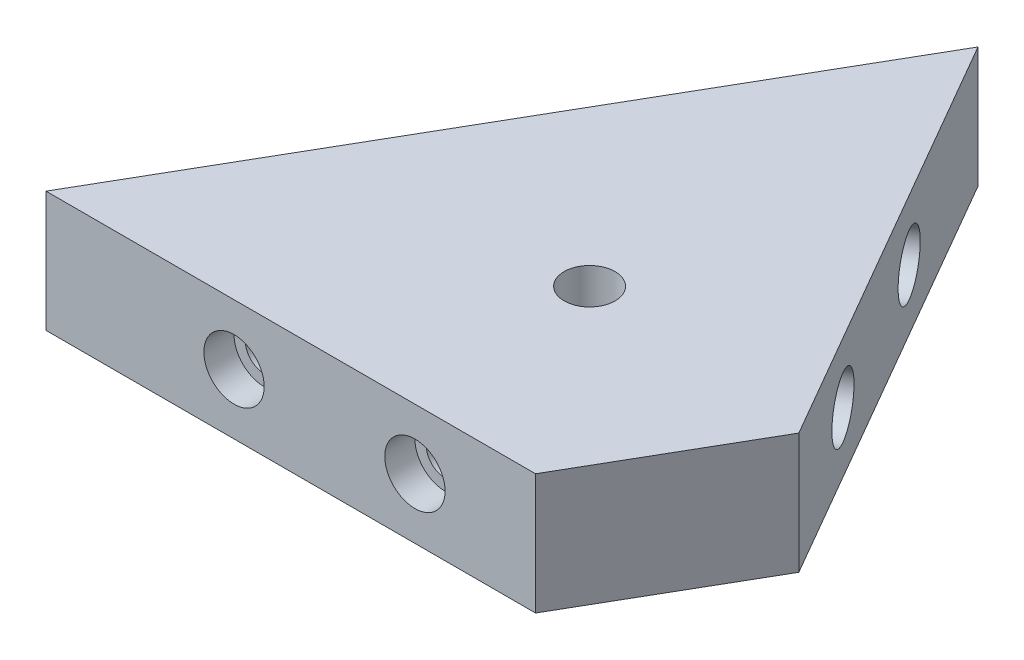
SolidWorks part; units mm, degrees
material "Cast Carbon Steel"
ref_plane "Front Plane" through (0, 0, 0) normal (0, 0, 1) x (1, 0, 0)
ref_plane "Top Plane" through (0, 0, 0) normal (0, 1, 0) x (1, 0, 0)
ref_plane "Right Plane" through (0, 0, 0) normal (1, 0, 0) x (0, 0, -1)
sketch "Sketch1" plane through (0, 0, 0) normal (0, 1, 0) x (1, 0, 0)
  line L0 (159.6594, -241.1624) -> (-297.5406, 22.8022) construction
  line L1 (-145.1406, 286.7667) -> (-449.9406, -241.1624) construction
  line L2 (-449.9406, -241.1624) -> (159.6594, -241.1624) construction
  line L3 (159.6594, -241.1624) -> (-145.1406, 286.7667) construction
  line L4 (93.6683, -241.1624) -> (93.6683, -203.0624) construction
  line L5 (119.0683, -241.1624) -> (129.2161, -223.5859)
  line L6 (55.5683, -241.1624) -> (55.5683, -181.0653) construction
  line L7 (15.9736, -241.1624) -> (51.8951, -178.9446)
  line L8 (15.9736, -241.1624) -> (119.0683, -241.1624)
  line L9 (51.8951, -178.9446) -> (129.2161, -223.5859)
  line L10 (93.6683, -203.0624) -> (55.5683, -203.0624) construction
  dimension "D1" = 609.6
  dimension "D2" = 38.1
  dimension "D3" = 25.4
  dimension "D4" = 38.1
  dimension "D5" = 15.24
  dimension "D6" = 40.5911
  dimension "D7" = 103.0947
  dimension "D8" = 60
  dimension "D9" = 120
extrude "Boss-Extrude1" add sketch "Sketch1" along normal blind 25.4
sketch "Sketch2" plane through (0, 0, 241.1624) normal (0, 0, 1) x (1, 0, 0)
  line L0 (15.9736, 0) -> (119.0683, 0) construction
  line L1 (15.9736, 0) -> (15.9736, 25.4) construction
  line L2 (119.0683, 0) -> (119.0683, 25.4) construction
  line L3 (15.9736, 25.4) -> (119.0683, 25.4) construction
  line L4 (15.9736, 0) -> (119.0683, 25.4) construction
  line L5 (119.0683, 0) -> (15.9736, 25.4) construction
  line L6 (93.6683, 25.4) -> (93.6683, 0) construction
  line L7 (55.5683, 0) -> (55.5683, 25.4) construction
  circle A0 centre (55.5683, 12.7) radius 6.35
  circle A1 centre (93.6683, 12.7) radius 6.35
  point P6 (67.521, 12.7)
  dimension "D4" = 12.7
  dimension "D5" = 12.7
  dimension "D1" = 25.4
  dimension "D2" = 25.4
  dimension "D3" = 38.1
extrude "Cut-Extrude1" cut sketch "Sketch2" against normal blind 6.35
hole_wizard "3/8-16 Tapped Hole1" positions "Sketch8" profile "Sketch9" tap size "3/8-16" standard "ANSI Inch"
sketch "Sketch8" plane through (0, 0, 234.8124) normal (0, 0, 1) x (1, 0, 0)
  point P0 (93.6683, 12.7)
  point P3 (55.5683, 12.7)
sketch "Sketch9" plane through (93.6683, 12.7, 234.8124) normal (1, 0, 0) x (0, -1, 0)
  line L0 (0, 0) -> (0, 18.2597)
  line L1 (0, 18.2597) -> (3.9687, 15.875)
  line L2 (3.9687, 15.875) -> (3.9687, 0)
  line L5 (3.9687, 0) -> (0, 0)
  line L10 (0, 18.2597) -> (-3.9688, 15.875) construction
  line L11 (0, -6.35) -> (0, 107.95) construction
  dimension "Tap Drill Dia." = 7.9375
  dimension "Tap Drill Depth" = 15.875
  dimension "Drill Angle" = 118
mirror "Mirror1" about plane through (51.8951, 25.4, 178.9446) normal (-0.5, 0, 0.866) of "Boss-Extrude1", "Cut-Extrude1"
sketch "Sketch5" plane through (0, 25.4, 0) normal (0, 1, 0) x (1, 0, 0)
  line L0 (87.8165, -116.7268) -> (15.9736, -241.1624) construction
  line L1 (15.9736, -241.1624) -> (119.0683, -241.1624) construction
  line L2 (119.0683, -241.1624) -> (139.3639, -206.0094) construction
  line L3 (139.3639, -206.0094) -> (87.8165, -116.7268) construction
  line L4 (51.8951, -178.9446) -> (129.2161, -223.5859) construction
  point P13 (90.5556, -201.2653)
  point P15 (90.5556, -201.2653)
  dimension "D3" = 71.8429
hole_wizard "1/2-13 Tapped Hole1" positions "Sketch5" profile "Sketch7" tap size "1/2-13" standard "ANSI Inch" end condition through all
sketch "Sketch7" plane through (90.5556, 25.4, 201.2653) normal (1, 0, 0) x (0, 0, 1)
  line L0 (0, 0) -> (0, 25.4)
  line L1 (0, 25.4) -> (5.3581, 25.4)
  line L2 (5.3581, 25.4) -> (5.3581, 0)
  line L5 (5.3581, 0) -> (0, 0)
  line L11 (0, -6.35) -> (0, 107.95) construction
  dimension "Thru Tap Drill Dia." = 10.7163
  dimension "Thru Tap Drill Depth" = 25.4
cosmetic thread "Hole Thread1" parameters "D2"=12.7
cosmetic thread "Hole Thread2" parameters "D2"=12.7
hole_wizard "3/8-16 Tapped Hole2" positions "Sketch10" profile "Sketch11" tap size "3/8-16" standard "ANSI Inch"
sketch "Sketch10" plane through (9.8189, 0, -5.669) normal (0.866, 0, -0.5) x (-0.5, 0, -0.866)
  point P0 (-184.5913, 12.7)
  point P3 (-222.6913, 12.7)
sketch "Sketch11" plane through (102.1146, 12.7, 154.1918) normal (0, 1, 0) x (-0.5, 0, -0.866)
  line L0 (0, 0) -> (0, 18.2597)
  line L1 (0, 18.2597) -> (3.9687, 15.875)
  line L2 (3.9687, 15.875) -> (3.9687, 0)
  line L5 (3.9687, 0) -> (0, 0)
  line L10 (0, 18.2597) -> (-3.9688, 15.875) construction
  line L11 (0, -6.35) -> (0, 107.95) construction
  dimension "Tap Drill Dia." = 7.9375
  dimension "Tap Drill Depth" = 15.875
  dimension "Drill Angle" = 118
